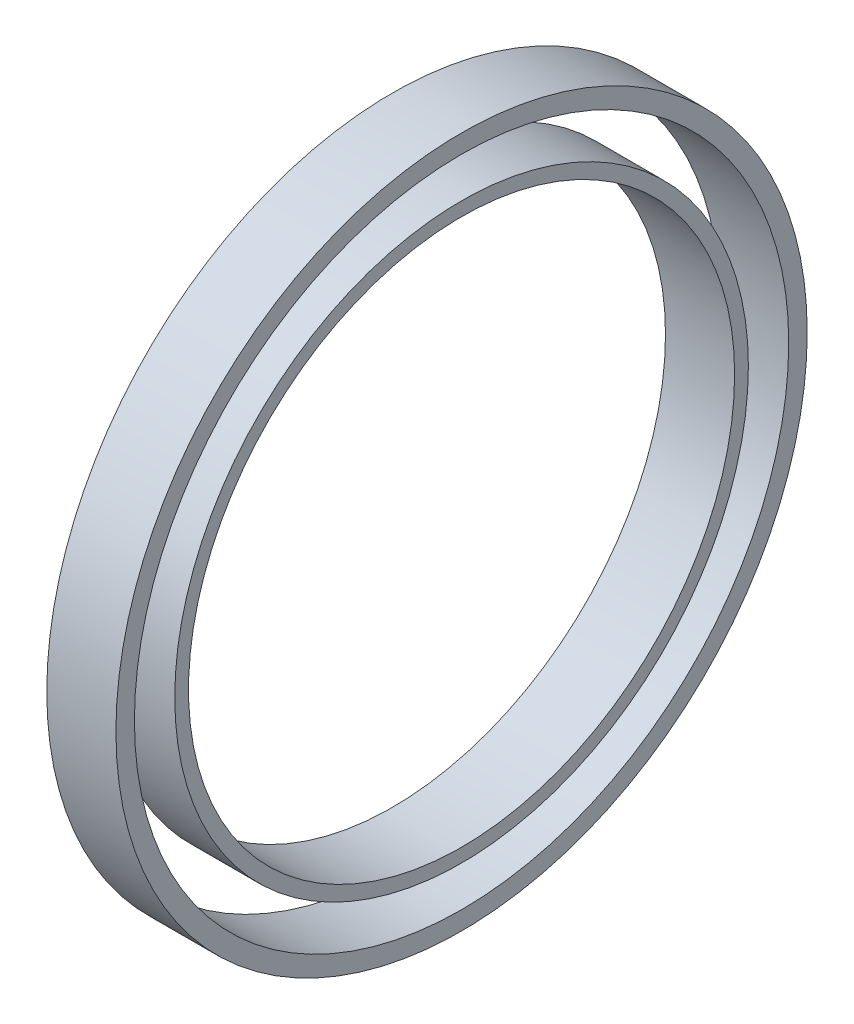
SolidWorks part; units mm, degrees
material "PBT General Purpose"
ref_plane "Front Plane" through (0, 0, 0) normal (0, 0, 1) x (1, 0, 0)
ref_plane "Top Plane" through (0, 0, 0) normal (0, 1, 0) x (1, 0, 0)
ref_plane "Right Plane" through (0, 0, 0) normal (1, 0, 0) x (0, 0, -1)
sketch "Sketch1" plane through (0, 0, 0) normal (1, 0, 0) x (0, 0, -1)
  circle A0 centre (0, 0) radius 20.066
  circle A1 centre (0, 0) radius 25.4
extrude "Boss-Extrude1" add sketch "Sketch1" along normal blind 5.08
sketch "Sketch2" plane through (0, 0, 0) normal (-1, 0, 0) x (0, 0, 1)
  circle A0 centre (0, 0) radius 21.0767
  circle A1 centre (0, 0) radius 24.041
extrude "Cut-Extrude1" cut sketch "Sketch2" against normal blind 12.7
sketch "Sketch3" plane through (0, 0, 0) normal (-1, 0, 0) x (0, 0, 1)
  line L1 (0, 21.0767) -> (2.3342, 22.4958)
  line L2 (2.3342, 22.4958) -> (0, 24.041)
  line L3 (1.2019, 24.0109) -> (3.5616, 22.4958)
  line L4 (3.5616, 22.4958) -> (1.2019, 21.0424)
  circle A0 centre (0, 0) radius 24.041 construction
  circle A1 centre (0, 0) radius 21.0767 construction
  arc A2 (0, 24.041) -> (1.2019, 24.0109) centre (0, 0) cw
  arc A3 (0, 21.0767) -> (1.2019, 21.0424) centre (0, 0) cw
extrude "Boss-Extrude2" [suppressed] add sketch "Sketch3" against normal blind 12.7
mirror "Mirror1" [suppressed] about plane through (0, 0, 0) normal (0, 0, 1)
pattern_circular "CirPattern2" [suppressed] count 15 over 360 of bodies 106
sketch "Sketch4" plane through (0, 0, 0) normal (-1, 0, 0) x (0, 0, 1)
  line L3 (0.2578, 20.4756) -> (-0.2578, 20.4756)
  line L4 (0.2578, 20.4756) -> (0.2578, 24.3623)
  line L5 (0.2578, 24.3623) -> (-0.2578, 24.3623)
  line L6 (-0.2578, 20.4756) -> (-0.2578, 24.3623)
  line L7 (0.2578, 20.4756) -> (-0.2578, 24.3623) construction
  line L8 (0.2578, 24.3623) -> (-0.2578, 20.4756) construction
  point P0 (0, 22.419)
extrude "Boss-Extrude3" [suppressed] add sketch "Sketch4" against normal blind 12.7
pattern_circular "CirPattern3" [suppressed] count 30 over 360 of bodies 108
ref_plane "Plane1" through (0, 0, 20.6284) normal (0, 0, 1) x (1, 0, 0)
sketch "Sketch5" plane through (0, 0, 20.6284) normal (0, 0, 1) x (1, 0, 0)
  circle A0 centre (6.35, 0) radius 1.5875
extrude "Boss-Extrude5" [suppressed] add sketch "Sketch5" along normal blind 4.064
pattern_circular "CirPattern4" [suppressed] count 17 over 360 of bodies 111
